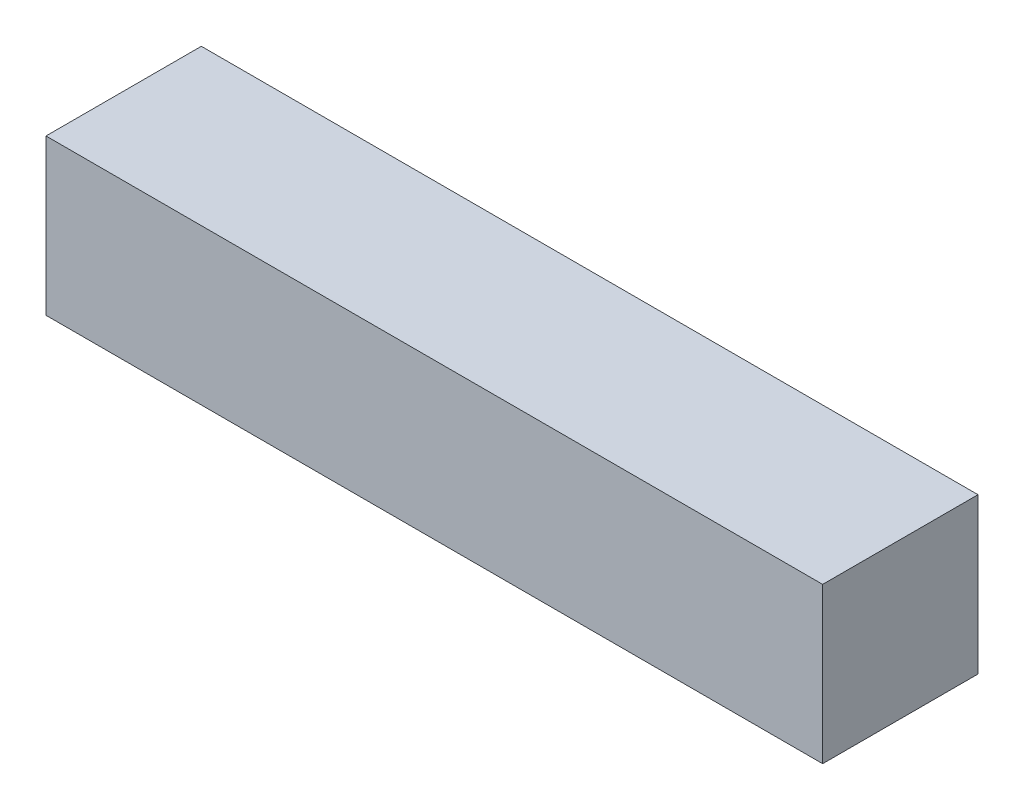
SolidWorks part; units mm, degrees
ref_plane "Front Plane" through (0, 0, 0) normal (0, 0, 1) x (1, 0, 0)
ref_plane "Top Plane" through (0, 0, 0) normal (0, 1, 0) x (1, 0, 0)
ref_plane "Right Plane" through (0, 0, 0) normal (1, 0, 0) x (0, 0, -1)
sketch "Sketch2" plane through (0, 0, 0) normal (1, 0, 0) x (0, 0, -1)
  line L1 (-10, -10) -> (10, -10)
  line L2 (-10, -10) -> (-10, 10)
  line L3 (-10, 10) -> (10, 10)
  line L4 (10, -10) -> (10, 10)
  line L5 (-10, -10) -> (10, 10) construction
  line L6 (-10, 10) -> (10, -10) construction
  point P0 (0, 0)
  dimension "D1" = 20
  dimension "D2" = 20
extrude "Boss-Extrude1" add sketch "Sketch2" along normal blind 50 and the other way blind 50
